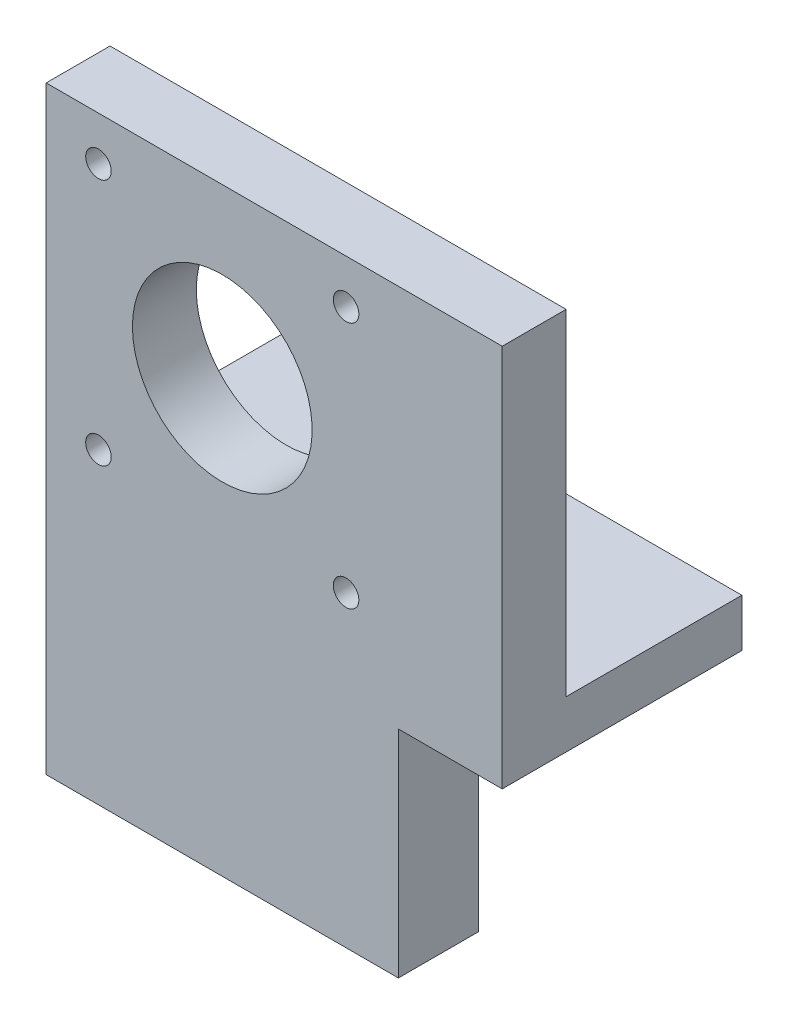
SolidWorks part; units mm, degrees
ref_plane "Front Plane" through (0, 0, 0) normal (0, 0, 1) x (1, 0, 0)
ref_plane "Top Plane" through (0, 0, 0) normal (0, 1, 0) x (1, 0, 0)
ref_plane "Right Plane" through (0, 0, 0) normal (1, 0, 0) x (0, 0, -1)
sketch "Sketch1" plane through (0, 0, 0) normal (0, 1, 0) x (1, 0, 0)
  line L1 (-8, 7.5) -> (8, 7.5) construction
  line L2 (-8, 7.5) -> (-8, -7.5) construction
  line L3 (-8, -7.5) -> (8, -7.5) construction
  line L4 (8, 7.5) -> (8, -7.5) construction
  line L5 (-8, 7.5) -> (8, -7.5) construction
  line L6 (-8, -7.5) -> (8, 7.5) construction
  line L7 (-22.05, 10) -> (22.05, 10) construction
  line L8 (-22.05, 10) -> (-22.05, -10) construction
  line L9 (-22.05, -10) -> (22.05, -10) construction
  line L10 (22.05, 10) -> (22.05, -10) construction
  line L11 (-22.05, 10) -> (22.05, -10) construction
  line L12 (-22.05, -10) -> (22.05, 10) construction
  line L13 (-22.05, -10) -> (22.05, -10) construction
  line L14 (-22.05, -10) -> (-22.05, -20) construction
  line L15 (-22.05, -20) -> (22.05, -20) construction
  line L16 (22.05, -10) -> (22.05, -20) construction
  point P0 (0, 0)
  point P1 (8, -7.5)
  point P2 (-8, 7.5)
  point P3 (-8, -7.5)
  point P4 (8, 7.5)
  point P6 (0, 0)
  point P18 (-8, 7.5)
  dimension "D1" = 16
  dimension "D2" = 15
  dimension "D3" = 20
  dimension "D4" = 44.1
  dimension "D5" = 10
sketch "Sketch3" plane through (0, 0, 0) normal (0, 1, 0) x (1, 0, 0)
  line L1 (-22.05, 10) -> (22.05, 10)
  line L2 (-22.05, 10) -> (-22.05, -20)
  line L3 (-22.05, -20) -> (22.05, -20)
  line L4 (22.05, 10) -> (22.05, -20)
extrude "Boss-Extrude1" add sketch "Sketch3" against normal blind 8
sketch "Sketch4" plane through (0, -8, 0) normal (0, -1, 0) x (1, 0, 0)
  line L1 (-22.05, 20) -> (22.05, 20)
  line L2 (-22.05, 20) -> (-22.05, 10)
  line L3 (-22.05, 10) -> (22.05, 10)
  line L4 (22.05, 20) -> (22.05, 10)
extrude "Boss-Extrude2" add sketch "Sketch4" along normal blind 25
sketch "Sketch8" plane through (0, 0, 0) normal (0, 1, 0) x (1, 0, 0)
  point P0 (8, -7.5)
  point P2 (-8, -7.5)
  point P4 (8, 7.5)
  point P6 (-8, 7.5)
hole_wizard "CSK for M3 Flat Head Machine Screw1" positions "Sketch8" profile "Sketch9" countersink size "M3" standard "ANSI Metric" end condition through all
sketch "Sketch9" plane through (8, 0, 7.5) normal (1, 0, 0) x (0, 0, 1)
  line L0 (0, 0) -> (0, 33)
  line L1 (0, 33) -> (1.6, 33)
  line L2 (1.6, 33) -> (1.6, 1.55)
  line L3 (1.6, 1.55) -> (3.15, 0)
  line L5 (3.15, 0) -> (0, 0)
  line L6 (-1.6, 1.55) -> (-3.15, 0) construction
  line L11 (0, -6.35) -> (0, 107.95) construction
  dimension "Thru Hole Dia." = 3.2
  dimension "Thru Hole Depth" = 33
  dimension "Near C'Sink Dia." = 6.3
  dimension "Near C'Sink Angle" = 90
sketch "Sketch10" plane through (0, 0, 0) normal (0, 1, 0) x (1, 0, 0)
  line L0 (-22.05, -10) -> (-22.05, -20) construction
  line L1 (-22.05, -12) -> (22.05, -12)
  line L2 (-22.05, -12) -> (-22.05, -20)
  line L3 (-22.05, -20) -> (22.05, -20)
  line L4 (22.05, -12) -> (22.05, -20)
  line L5 (22.05, -10) -> (22.05, -20) construction
  line L6 (-22.05, -10) -> (22.05, -10) construction
  dimension "D1" = 2
  dimension "D2" = 8
extrude "Boss-Extrude3" add sketch "Sketch10" along normal blind 42
sketch "Sketch11" plane through (0, 0, 12) normal (0, 0, -1) x (-1, 0, 0)
  line L0 (22.05, 21) -> (0, 21) construction
  line L1 (-15.5, 36.5) -> (15.5, 36.5) construction
  line L2 (-15.5, 36.5) -> (-15.5, 5.5) construction
  line L3 (-15.5, 5.5) -> (15.5, 5.5) construction
  line L4 (15.5, 36.5) -> (15.5, 5.5) construction
  line L5 (22.05, 42) -> (22.05, 0) construction
  line L6 (-22.05, 42) -> (22.05, 42) construction
  line L7 (0, 42) -> (0, 21) construction
  circle A0 centre (0, 21) radius 11.25
  point P9 (0, 42)
  point P10 (22.05, 21)
  point P13 (0, 36.5)
  point P15 (15.5, 21)
  point P16 (15.5, 21)
  dimension "D5" = 22.5
  dimension "D3" = 31
  dimension "D4" = 31
extrude "Cut-Extrude1" cut sketch "Sketch11" against normal blind 42
sketch "Sketch12" plane through (0, 0, 12) normal (0, 0, -1) x (-1, 0, 0)
  point P0 (15.5, 5.5)
  point P2 (-15.5, 5.5)
  point P4 (15.5, 36.5)
  point P6 (-15.5, 36.5)
hole_wizard "M3 Clearance Hole4" positions "Sketch12" profile "Sketch13" hole size "M3" standard "ANSI Metric" end condition through all
sketch "Sketch13" plane through (-15.5, 5.5, 12) normal (1, 0, 0) x (0, 1, 0)
  line L0 (0, 0) -> (0, 8)
  line L1 (0, 8) -> (1.6, 8)
  line L2 (1.6, 8) -> (1.6, 0)
  line L5 (1.6, 0) -> (0, 0)
  line L11 (0, -6.35) -> (0, 107.95) construction
  dimension "Thru Hole Dia." = 3.2
  dimension "Thru Hole Depth" = 8
sketch "Sketch14" plane through (22.05, 0, 0) normal (1, 0, 0) x (0, 0, -1)
  line L0 (10, 0) -> (-10, 0) construction
  line L1 (10, 0) -> (-10, 0)
  line L2 (10, 0) -> (10, -6)
  line L3 (10, -6) -> (-10, -6)
  line L5 (10, 0) -> (-10, 0) construction
  line L6 (-10, 0) -> (-12, 0)
  line L7 (-20, 42) -> (-12, 42)
  line L8 (-20, 42) -> (-20, -6)
  line L9 (-20, -6) -> (-12, -6)
  line L10 (-12, 42) -> (-12, 0)
  line L11 (-10, 0) -> (-20, 0) construction
  line L12 (-10, -6) -> (-12, -6)
  dimension "D1" = 6
  dimension "D2" = 20
extrude "Boss-Extrude4" add sketch "Sketch14" along normal blind 13
sketch "Sketch15" plane through (-22.05, 0, 0) normal (-1, 0, 0) x (0, 0, 1)
  line L8 (12, 0) -> (-10, 0)
  line L9 (-10, 0) -> (-10, -8)
  line L10 (-10, -8) -> (10, -8)
  line L11 (10, -8) -> (10, -33)
  line L12 (10, -33) -> (20, -33)
  line L13 (20, -33) -> (20, 42)
  line L14 (20, 42) -> (12, 42)
  line L15 (12, 42) -> (12, 0)
  line L16 (12, 0) -> (-10, 0)
  line L17 (-10, 0) -> (-10, -8)
  line L18 (-10, -8) -> (10, -8)
  line L19 (10, -8) -> (10, -33)
  line L20 (10, -33) -> (20, -33)
  line L21 (20, -33) -> (20, 42)
  line L22 (20, 42) -> (12, 42)
  line L23 (12, 42) -> (12, 0)
  dimension "D1" = 0
chamfer "Chamfer2" distance 2 angle 45 1 edges at (-22.05, -8, 0)
